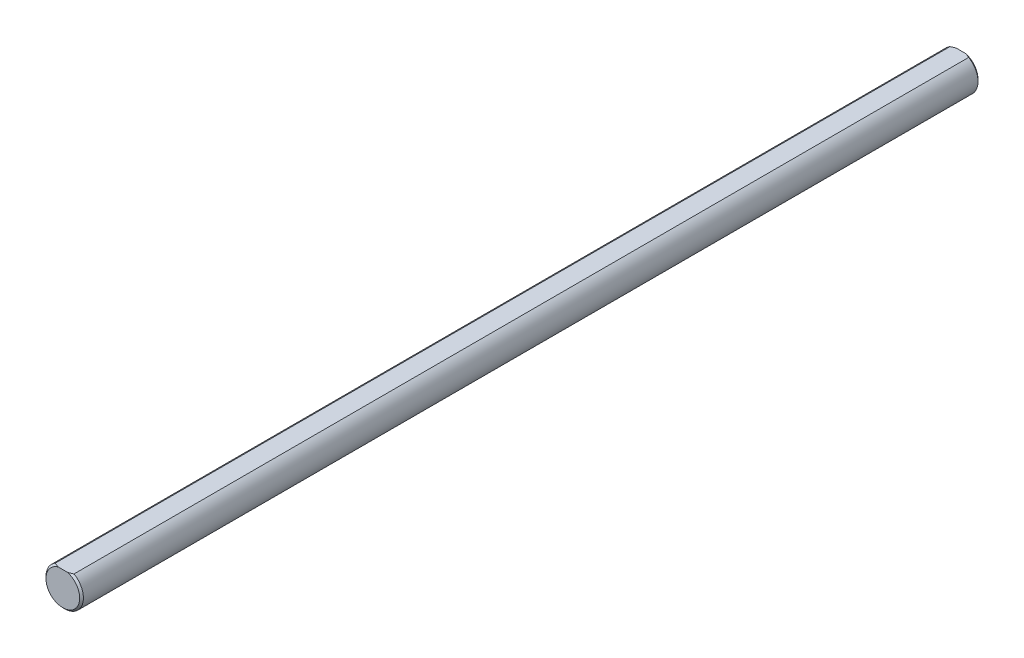
SolidWorks part; units mm, degrees
ref_plane "Front Plane" through (0, 0, 0) normal (0, 0, 1) x (1, 0, 0)
ref_plane "Top Plane" through (0, 0, 0) normal (0, 1, 0) x (1, 0, 0)
ref_plane "Right Plane" through (0, 0, 0) normal (1, 0, 0) x (0, 0, -1)
sketch "Sketch1" plane through (0, 0, 0) normal (0, 0, 1) x (1, 0, 0)
  line L0 (-1.5875, 2.7496) -> (1.5875, 2.7496) construction
  circle A1 centre (0, 0) radius 3.175 construction
  dimension "Diameter" = 6.35
  dimension "Flat Width" = 3.175
sketch "Sketch2" plane through (0, 0, 0) normal (1, 0, 0) x (0, 0, -1)
  line L0 (-76.2, 3.175) -> (76.2, 3.175) construction
  line L1 (0, 3.175) -> (0, -3.175) construction
  line L2 (0, 3.175) -> (0, -3.175) construction
  line L3 (-76.2, 3.175) -> (-76.2, -3.175) construction
  line L4 (-76.2, -3.175) -> (76.2, -3.175) construction
  point P2 (0, 3.175)
  point P3 (63.5, 3.175)
  point P4 (-63.5, 3.175)
  dimension "Length" = 152.4
  dimension "D2" = 12.7
  dimension "D1" = 12.7
  dimension "D-Profile Length" = 152.4
sketch "Sketch3" plane through (0, 0, 0) normal (0, 0, 1) x (1, 0, 0)
  circle A1 centre (0, 0) radius 3.175 construction
  circle A3 centre (0, 0) radius 3.175
extrude "Boss-Extrude2" add sketch "Sketch3" along normal up to vertex (76.2 mm away) and the other way up to vertex (76.2 mm away) up to point (0, 3.175, 76.2) other way up to point (0, 3.175, -76.2)
sketch "Sketch10" plane through (0, 0, 0) normal (0, 0, 1) x (1, 0, 0)
  line L0 (-1.5875, 2.7496) -> (1.5875, 2.7496)
  line L1 (0, 0) -> (0, 3.175) construction
  circle A0 centre (0, 0) radius 3.175 construction
  circle A1 centre (0, 0) radius 3.175 construction
  arc A2 (-1.5875, 2.7496) -> (1.5875, 2.7496) centre (0, 0) cw
extrude "Cut-Extrude5" cut sketch "Sketch10" against normal through all both and the other way through all
chamfer "Chamfer1" distance 0.3175 angle 45 2 edges at (0, -3.175, 76.2) (0, -3.175, -76.2)
equation "\"D1@Chamfer1\"= \"Diameter@Sketch1\" / 20"
equation "\"D1@Sketch2\"=\"Diameter@Sketch1\"*2"
equation "\"D2@Sketch2\"=\"D1@Sketch2\""
